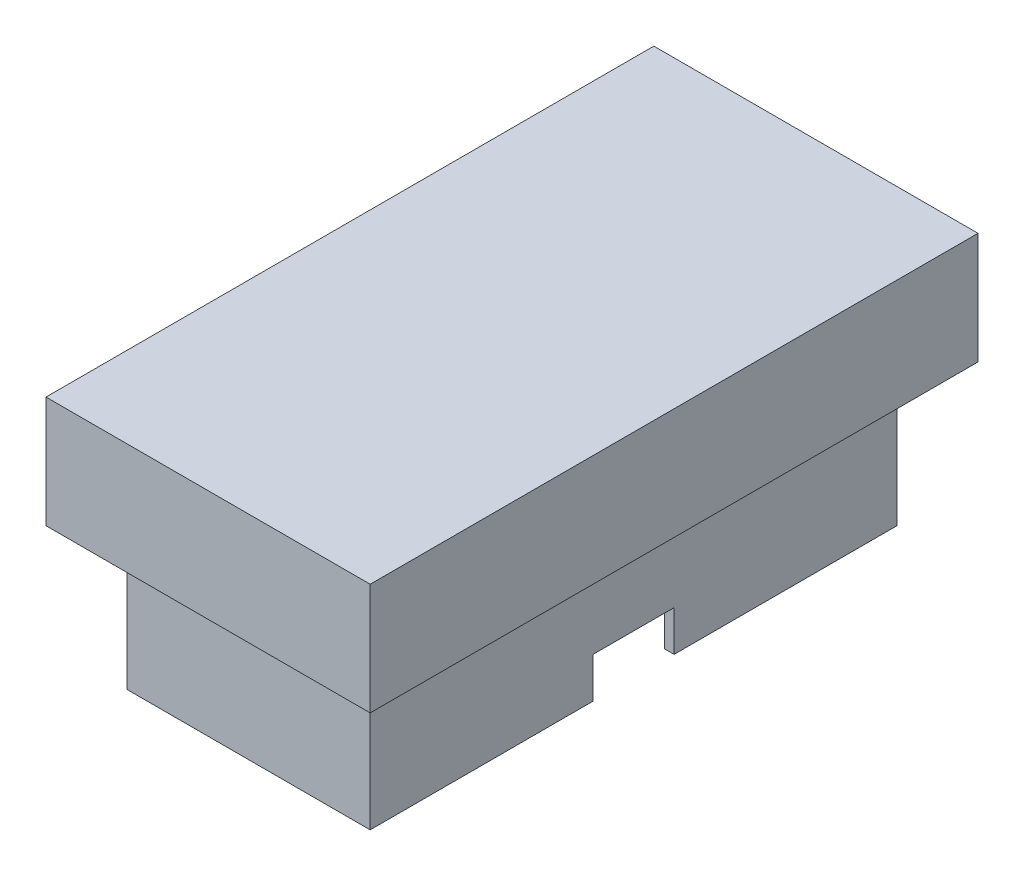
SolidWorks part; units mm, degrees
ref_plane "Front Plane" through (0, 0, 0) normal (0, 0, 1) x (1, 0, 0)
ref_plane "Top Plane" through (0, 0, 0) normal (0, 1, 0) x (1, 0, 0)
ref_plane "Right Plane" through (0, 0, 0) normal (1, 0, 0) x (0, 0, -1)
sketch "Sketch1" plane through (0, 0, 0) normal (0, 1, 0) x (1, 0, 0)
  line L1 (-3, -6.5) -> (3, -6.5)
  line L2 (-3, -6.5) -> (-3, 6.5)
  line L3 (-3, 6.5) -> (3, 6.5)
  line L4 (3, -6.5) -> (3, 6.5)
  line L5 (-3, -6.5) -> (3, 6.5) construction
  line L6 (-3, 6.5) -> (3, -6.5) construction
  line L7 (-2.7692, -6) -> (2.7692, -6)
  line L8 (-2.7692, -6) -> (-2.7692, 6)
  line L9 (-2.7692, 6) -> (2.7692, 6)
  line L10 (2.7692, -6) -> (2.7692, 6)
  line L11 (-2.7692, -6) -> (2.7692, 6) construction
  line L12 (-2.7692, 6) -> (2.7692, -6) construction
  point P0 (0, 0)
  point P6 (0, 0)
  dimension "D1" = 13
  dimension "D2" = 12
  dimension "D3" = 6
extrude "Boss-Extrude1" add sketch "Sketch1" along normal blind 3.5
sketch "Sketch3" plane through (3, 0, 0) normal (1, 0, 0) x (0, 0, -1)
  line L0 (-6.5, 0) -> (6.5, 0) construction
  line L1 (1, 0) -> (-1, 0)
  line L2 (1, 0) -> (1, 1)
  line L3 (1, 1) -> (-1, 1)
  line L4 (-1, 0) -> (-1, 1)
  line L5 (6.5, 3.5) -> (6.5, 0) construction
  dimension "D1" = 5.5
  dimension "D2" = 2
  dimension "D3" = 1
extrude "Cut-Extrude1" cut sketch "Sketch3" against normal through all both and the other way through all
sketch "Sketch4" plane through (0, 3.5, 0) normal (0, 1, 0) x (1, 0, 0)
  line L1 (-4, -7.5) -> (4, -7.5)
  line L2 (-4, -7.5) -> (-4, 7.5)
  line L3 (-4, 7.5) -> (4, 7.5)
  line L4 (4, -7.5) -> (4, 7.5)
  line L5 (-4, -7.5) -> (4, 7.5) construction
  line L6 (-4, 7.5) -> (4, -7.5) construction
  line L7 (-3.5, -6.5625) -> (3.5, -6.5625)
  line L8 (-3.5, -6.5625) -> (-3.5, 6.5625)
  line L9 (-3.5, 6.5625) -> (3.5, 6.5625)
  line L10 (3.5, -6.5625) -> (3.5, 6.5625)
  line L11 (-3.5, -6.5625) -> (3.5, 6.5625) construction
  line L12 (-3.5, 6.5625) -> (3.5, -6.5625) construction
  point P0 (0, 0)
  point P6 (0, 0)
  dimension "D1" = 15
  dimension "D2" = 8
  dimension "D3" = 7
extrude "Boss-Extrude2" add sketch "Sketch4" along normal blind 2.5 separate body
sketch "Sketch5" plane through (0, 3.5, 0) normal (0, -1, 0) x (1, 0, 0)
  line L1 (-3.5, 6.5625) -> (3.5, 6.5625)
  line L2 (-3.5, 6.5625) -> (-3.5, -6.5625)
  line L3 (-3.5, -6.5625) -> (3.5, -6.5625)
  line L4 (3.5, 6.5625) -> (3.5, -6.5625)
extrude "Boss-Extrude3" add sketch "Sketch5" along normal blind 0.5
sketch "Sketch6" plane through (0, 3, 0) normal (0, -1, 0) x (1, 0, 0)
  line L1 (-2.7692, -6) -> (2.7692, -6)
  line L2 (-2.7692, -6) -> (-2.7692, 6)
  line L3 (-2.7692, 6) -> (2.7692, 6)
  line L4 (2.7692, -6) -> (2.7692, 6)
extrude "Cut-Extrude2" cut sketch "Sketch6" against normal through all both and the other way through all
sketch "Sketch7" plane through (0, 6, 0) normal (0, 1, 0) x (1, 0, 0)
  line L1 (-4, -7.5) -> (4, -7.5)
  line L2 (-4, -7.5) -> (-4, 7.5)
  line L3 (-4, 7.5) -> (4, 7.5)
  line L4 (4, -7.5) -> (4, 7.5)
extrude "Boss-Extrude4" add sketch "Sketch7" along normal blind 0.25
